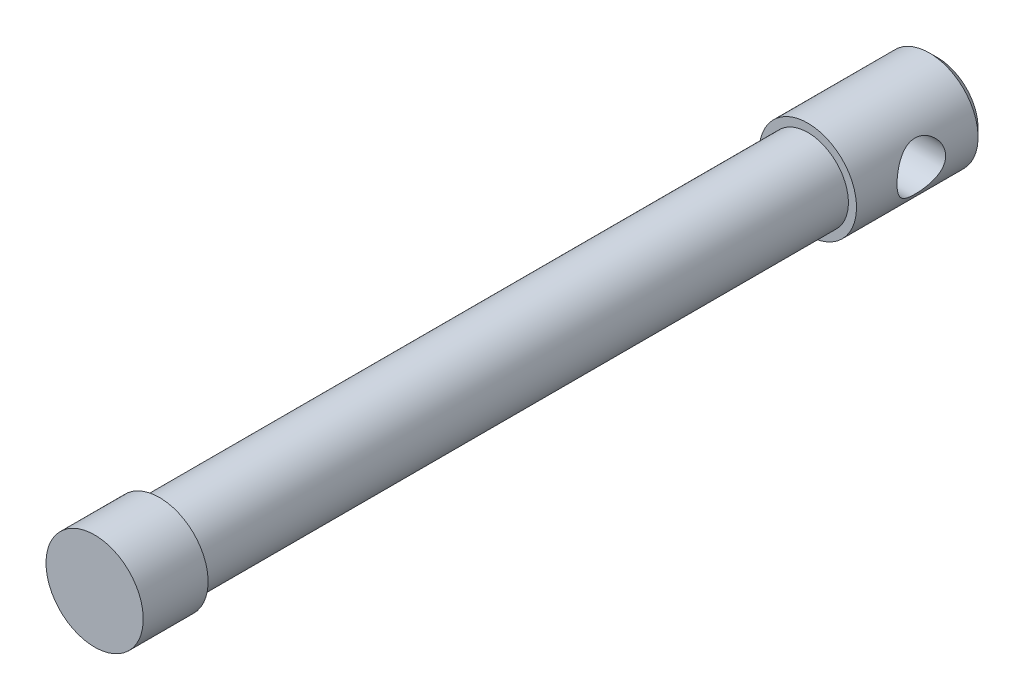
SolidWorks part; units mm, degrees
material "Alloy Steel"
ref_plane "Front Plane" through (0, 0, 0) normal (0, 0, 1) x (1, 0, 0)
ref_plane "Top Plane" through (0, 0, 0) normal (0, 1, 0) x (1, 0, 0)
ref_plane "Right Plane" through (0, 0, 0) normal (1, 0, 0) x (0, 0, -1)
sketch3d "3DSketch2"
  line L0 (0, 0, 0) -> (0, 0, -165.1)
  circle A0 centre (0, 0, 0) radius 9.525
  circle A1 centre (0, 0, -12.7) radius 9.525
  circle A2 centre (0, 0, -12.7) radius 7.9375
  circle A3 centre (0, 0, -165.1) radius 9.525
  circle A4 centre (0, 0, -139.7) radius 9.525
  circle A5 centre (0, 0, -139.7) radius 7.9375
  point P4 (0, 0, 9.525)
  point P7 (0, 0, -3.175)
  point P9 (0, 0, -4.7625)
  point P11 (0, 0, -155.575)
  point P14 (0, 0, -130.175)
  point P16 (0, 0, -131.7625)
  dimension "D2" = 19.05
  dimension "D3" = 19.05
  dimension "D5" = 15.875
  dimension "D6" = 19.05
  dimension "D7" = 19.05
  dimension "D9" = 15.875
  dimension "D1" = 165.1
  dimension "D4" = 12.7
  dimension "D8" = 25.4
extrude "Boss-Extrude1" add sketch "3DSketch2" along direction (0, 0, -1) on the side of the normal blind 12.7 contours A0
sketch "Sketch1" plane through (0, 0, -12.7) normal (0, 0, -1) x (-1, 0, 0)
  circle A0 centre (0, 0) radius 7.9375
  dimension "D1" = 15.875
extrude "Boss-Extrude2" add sketch "Sketch1" along normal blind 127
sketch "Sketch2" plane through (0, 0, -139.7) normal (0, 0, -1) x (-1, 0, 0)
  circle A0 centre (0, 0) radius 9.525
  dimension "D1" = 19.05
extrude "Boss-Extrude3" add sketch "Sketch2" along normal blind 25.4
chamfer "Chamfer2" distance 1.5875 angle 45 1 edges at (-9.525, 0, -165.1)
sketch "Sketch3" plane through (0, 0, 0) normal (1, 0, 0) x (0, 0, -1)
  line L0 (165.1, -7.9375) -> (165.1, 7.9375) construction
  circle A0 centre (152.4, 0) radius 4.7625
  point P0 (152.4, 0)
  dimension "D2" = 9.525
  dimension "D1" = 12.7
extrude "Cut-Extrude1" cut sketch "Sketch3" against normal through all both and the other way through all
